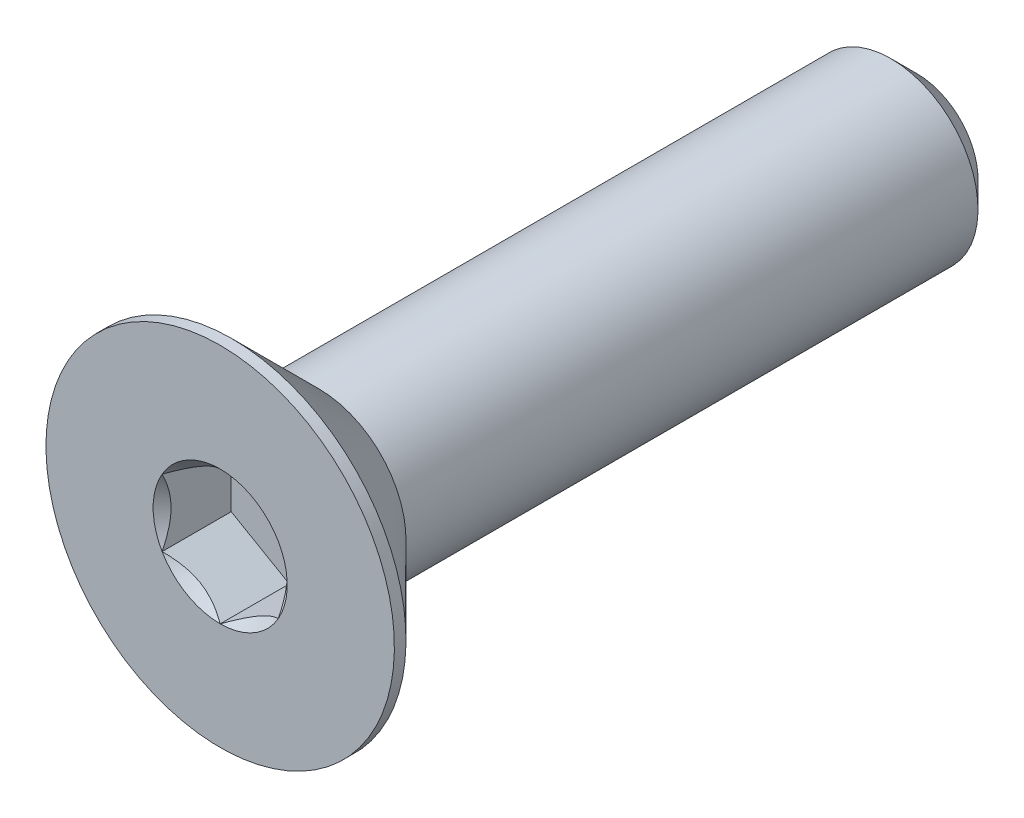
SolidWorks part; units mm, degrees
material "Alloy Steel"
ref_plane "Front" through (0, 0, 0) normal (0, 0, 1) x (1, 0, 0)
ref_plane "Top" through (0, 0, 0) normal (0, 1, 0) x (1, 0, 0)
ref_plane "Right" through (0, 0, 0) normal (1, 0, 0) x (0, 0, -1)
sketch "Sketch1" plane through (0, 0, 0) normal (1, 0, 0) x (0, 0, -1)
  line L0 (-6, 3) -> (-5.8, 3) construction
  line L1 (-5.8, 3) -> (-4.3, 1.5) construction
  line L2 (-6, 1.5) -> (6, 1.5) construction
  line L3 (6, 1.5) -> (6, 0) construction
  line L4 (6, 0) -> (-6, 0) construction
  line L5 (-6, 0) -> (-6, 3) construction
  line L6 (-6, 3) -> (-6, -3) construction
  line L7 (6, 1.5) -> (6, -1.5) construction
  line L8 (-6, -3) -> (-5.8, -3) construction
  line L9 (-5.8, -3) -> (-4.3, -1.5) construction
  line L11 (-6, 1.5) -> (-6, 0) construction
  line L12 (-4.3, 1.5) -> (-4.3, 0) construction
  line L13 (5.9688, 1.5541) -> (6.2188, 1.1211) construction
  line L14 (6.2188, 1.1211) -> (6.4687, 1.5541) construction
  line L15 (6.4687, 1.5541) -> (5.9688, 1.5541) construction
  line L16 (6.2188, 1.5541) -> (6.2188, 1.5) construction
  line L17 (6.2188, 1.5) -> (6.2188, 1.1752) construction
  line L18 (6.2188, 1.1752) -> (6.2188, 1.1211) construction
  line L19 (6.2188, 1.5271) -> (6.4531, 1.5271) construction
  line L20 (6.2188, 1.5271) -> (5.9844, 1.5271) construction
  line L21 (6, 1.5) -> (6.4375, 1.5) construction
  line L22 (6.1875, 1.1752) -> (6.25, 1.1752) construction
  line L23 (6, -1.5) -> (-4.3, -1.5) construction
  point P10 (4.75, -1.5)
  point P24 (-4.3, 1.5)
  point P30 (0, 0)
  dimension "Head Diameter" = 6
  dimension "Head Height" = 1.7
  dimension "Length" = 12
  dimension "Countersink Angle" = 90
  dimension "Thread Pitch" = 0.5
  dimension "D2" = 0.0625
  dimension "Minimum Thread Length" = 10.3
  dimension "Thread Size" = 3
  dimension "D1" = 1.25
sketch "Sketch2" plane through (0, 0, 0) normal (0, 0, 1) x (1, 0, 0)
  line L1 (0, 1.1547) -> (-1, 0.5774) construction
  line L2 (-1, 0.5774) -> (-1, -0.5774) construction
  line L3 (-1, -0.5774) -> (0, -1.1547) construction
  line L4 (0, -1.1547) -> (1, -0.5774) construction
  line L5 (1, -0.5774) -> (1, 0.5774) construction
  line L6 (1, 0.5774) -> (0, 1.1547) construction
  circle A0 centre (0, 0) radius 1 construction
  dimension "Drive Size" = 2
sketch "Sketch3" plane through (0, 0, 0) normal (1, 0, 0) x (0, 0, -1)
  line L0 (-6, 1.5) -> (6, 1.5)
  line L1 (6, 1.5) -> (6, 0)
  line L2 (6, 0) -> (-6, 0)
  line L3 (-6, 0) -> (-6, 1.5)
revolve "Revolve1" add sketch "Sketch3" angle 360 about L4
chamfer "Chamfer1" distance 0.45 angle 45 1 edges at (0, 1.5, -6)
sketch "Sketch6" plane through (0, 0, 0) normal (1, 0, 0) x (0, 0, -1)
  line L0 (-6, 3) -> (-5.8, 3)
  line L1 (-5.8, 3) -> (-4.3, 1.5)
  line L2 (-4.3, 1.5) -> (-4.3, 0)
  line L3 (-4.3, 0) -> (-6, 0)
  line L4 (-6, 0) -> (-6, 3)
revolve "Revolve2" add sketch "Sketch6" angle 360 about L4
sketch "Sketch8" plane through (0, 0, 6) normal (0, 0, 1) x (1, 0, 0)
  line L0 (0, 1.1547) -> (-1, 0.5774) construction
  line L1 (1, 0.5774) -> (0, 1.1547) construction
  line L2 (1, -0.5774) -> (1, 0.5774) construction
  line L3 (0, -1.1547) -> (1, -0.5774) construction
  line L4 (-1, 0.5774) -> (-1, -0.5774) construction
  line L5 (-1, -0.5774) -> (0, -1.1547) construction
  line L6 (0, 1.1547) -> (-1, 0.5774)
  line L7 (1, 0.5774) -> (0, 1.1547)
  line L8 (1, -0.5774) -> (1, 0.5774)
  line L9 (0, -1.1547) -> (1, -0.5774)
  line L10 (-1, 0.5774) -> (-1, -0.5774)
  line L11 (-1, -0.5774) -> (0, -1.1547)
extrude "Cut-Extrude1" cut sketch "Sketch8" against normal blind 1.19
sketch "Sketch9" plane through (0, 0, 6) normal (0, 0, 1) x (1, 0, 0)
  circle A0 centre (0, 0) radius 1.1547
extrude "Cut-Extrude2" cut sketch "Sketch9" against normal up to next (1.19 mm away) draft 45
ref_plane "Plane1" [suppressed] through (0, 0, 4.3) normal (0, 0, 1) x (1, 0, 0)
split "Split1" [suppressed] bodies to split 124
sketch "Sketch4" [suppressed] plane through (0, 0, -6) normal (0, 0, -1) x (-1, 0, 0)
  circle A0 centre (0, 0) radius 1.5 construction
  circle A1 centre (0, 0) radius 1.5
curve "Helix/Spiral1" [suppressed] pitch 0.5 height 10.8 turns 21.6
sketch "Sketch10" [suppressed] plane through (0, 0, 0) normal (1, 0, 0) x (0, 0, -1)
  line L0 (5.9844, 1.5271) -> (6.4531, 1.5271)
  line L1 (6.4531, 1.5271) -> (6.25, 1.1752)
  line L2 (6.25, 1.1752) -> (6.1875, 1.1752)
  line L3 (6.1875, 1.1752) -> (5.9844, 1.5271)
sweep "Cut-Sweep1" [suppressed] cut profiles "Sketch10" path "Helix/Spiral1"
equation "\"D2@Sketch1\" = \"Thread Pitch@Sketch1\" / 8"
equation "\"D4@Helix/Spiral1\"=\"Thread Pitch@Sketch1\""
equation "\"D3@Helix/Spiral1\"=\"Minimum Thread Length@Sketch1\"+\"Thread Pitch@Sketch1\""
equation "\"D1@Chamfer1\"=\"Thread Size@Sketch1\"*.15"
equation "\"D1@Cut-Extrude1\"=\"Head Height@Sketch1\"*.7"
equation "\"D1@Sketch1\"=\"Thread Pitch@Sketch1\"*2.5"
